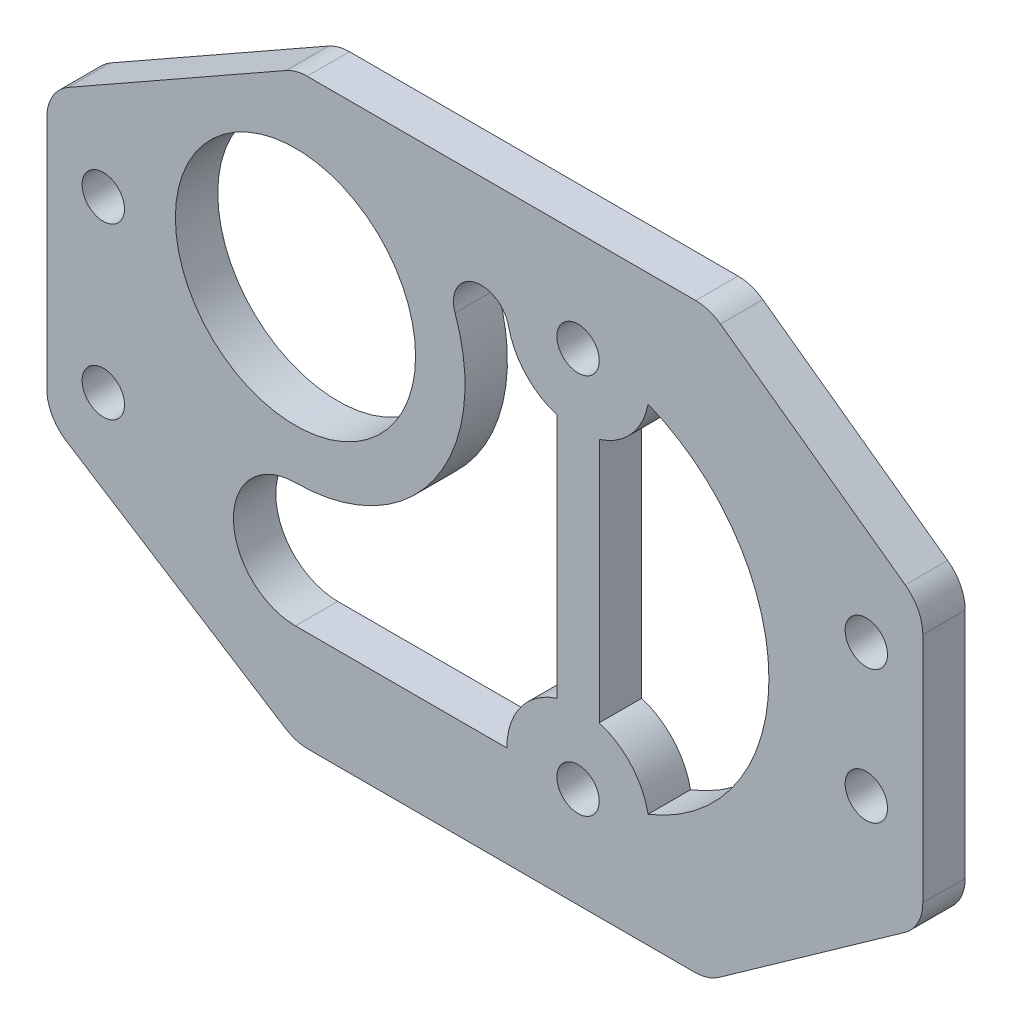
SolidWorks part; units mm, degrees
ref_plane "Front Plane" through (0, 0, 0) normal (0, 0, 1) x (1, 0, 0)
ref_plane "Top Plane" through (0, 0, 0) normal (0, 1, 0) x (1, 0, 0)
ref_plane "Right Plane" through (0, 0, 0) normal (1, 0, 0) x (0, 0, -1)
sketch "Sketch1" plane through (0, 0, 0) normal (0, 0, 1) x (1, 0, 0)
  line L0 (0, 1.648) -> (0, 18.258)
  line L1 (1.52, 20.8675) -> (16.9423, 29.6143)
  line L2 (18.4223, 30.0048) -> (45.9223, 30.0048)
  line L3 (47.6787, 29.4368) -> (60.7565, 19.9918)
  line L4 (62, 17.5597) -> (62, 1.1297)
  line L5 (60.736, -1.317) -> (47.5794, -10.6519)
  line L6 (45.8434, -11.2052) -> (18.5034, -11.2052)
  line L7 (16.8942, -10.7371) -> (1.3908, -0.8839)
  line L8 (1.3029, 15.3998) -> (6.6971, 15.3998) construction
  line L9 (0.2452, 3.3998) -> (7.7548, 3.3998) construction
  line L10 (17.6, 31.521) -> (17.6, -5.7675) construction
  line L11 (7.7548, 16.6798) -> (25.5136, 16.6798) construction
  line L12 (-39.3225, 9.3998) -> (106.4512, 9.3998) construction
  line L13 (39.1, 0.714) -> (39.1, 18.0856)
  line L14 (36.1, 18.0856) -> (36.1, 0.714)
  line L15 (37.6, 44.2333) -> (37.6, -14.3158) construction
  line L16 (32.5576, -4.1002) -> (17.6, -4.1002)
  arc A0 (18.5034, -11.2052) -> (16.8942, -10.7371) centre (18.5034, -8.2052) cw
  arc A1 (47.5794, -10.6519) -> (45.8434, -11.2052) centre (45.8434, -8.2052) cw
  arc A2 (60.7565, 19.9918) -> (62, 17.5597) centre (59, 17.5597) cw
  arc A3 (62, 1.1297) -> (60.736, -1.317) centre (59, 1.1297) cw
  arc A4 (45.9223, 30.0048) -> (47.6787, 29.4368) centre (45.9223, 27.0048) cw
  arc A5 (16.9423, 29.6143) -> (18.4223, 30.0048) centre (18.4223, 27.0048) cw
  arc A6 (0, 18.258) -> (1.52, 20.8675) centre (3, 18.258) cw
  arc A7 (0, 1.648) -> (1.3908, -0.8839) centre (3, 1.648) ccw
  circle A8 centre (4, 15.3998) radius 1.5
  circle A9 centre (4, 3.3998) radius 1.5
  circle A10 centre (58, 15.0918) radius 1.5
  circle A11 centre (58, 5.6783) radius 1.5
  circle A12 centre (37.6, 22.8998) radius 1.5
  circle A13 centre (37.6, -4.1002) radius 1.5
  circle A14 centre (17.6, 16.6798) radius 8.5
  arc A15 (36.1, 0.714) -> (32.5576, -4.1002) centre (37.6, -4.1002) ccw
  arc A16 (39.1, 18.0856) -> (42.5552, 21.966) centre (37.6, 22.8998) ccw
  arc A18 (32.6759, 21.814) -> (36.1, 18.0856) centre (37.6, 22.8998) ccw
  arc A19 (42.5552, -3.1664) -> (42.5552, 21.966) centre (37.6, 9.3998) ccw
  arc A20 (42.5552, -3.1664) -> (39.1, 0.714) centre (37.6, -4.1002) ccw
  arc A21 (17.6, 4.6798) -> (17.6, -4.1002) centre (17.6, 0.2898) ccw
  arc A22 (17.6, 4.6798) -> (28.8974, 20.7256) centre (17.6, 16.6798) ccw
  arc A23 (32.6759, 21.814) -> (28.8974, 20.7256) centre (30.7521, 21.3898) ccw
  point P15 (17.6307, -11.2052)
  point P18 (46.7996, -11.2052)
  point P21 (62, 19.0936)
  point P24 (62, -0.4201)
  point P27 (46.8923, 30.0048)
  point P30 (17.6307, 30.0048)
  point P33 (0, 20.0054)
  point P36 (0, 0)
  dimension "D8" = 3
  dimension "D9" = 3
  dimension "D10" = 3
  dimension "D11" = 3
  dimension "D12" = 3
  dimension "D13" = 3
  dimension "D14" = 3
  dimension "D16" = 3
  dimension "D27" = 17
  dimension "D28" = 12
  dimension "D30" = 4.71
  dimension "D31" = 24
  dimension "D32" = 3.94
  dimension "D1" = 209.56
  dimension "D2" = 41.21
  dimension "D3" = 62
  dimension "D4" = 27.34
  dimension "D5" = 27.5
  dimension "D6" = 17.73
  dimension "D7" = 16.61
  dimension "D15" = 16.43
  dimension "D17" = 4
  dimension "D18" = 6
  dimension "D19" = 4.9
  dimension "D20" = 4
  dimension "D21" = 20.4
  dimension "D22" = 27
  dimension "D23" = 7.105
  dimension "D24" = 17.6
  dimension "D25" = 20.605
  dimension "D26" = 7.28
  dimension "D29" = 3
other "AlignGroup1"
extrude "Boss-Extrude1" add sketch "Sketch1" along normal blind 3
